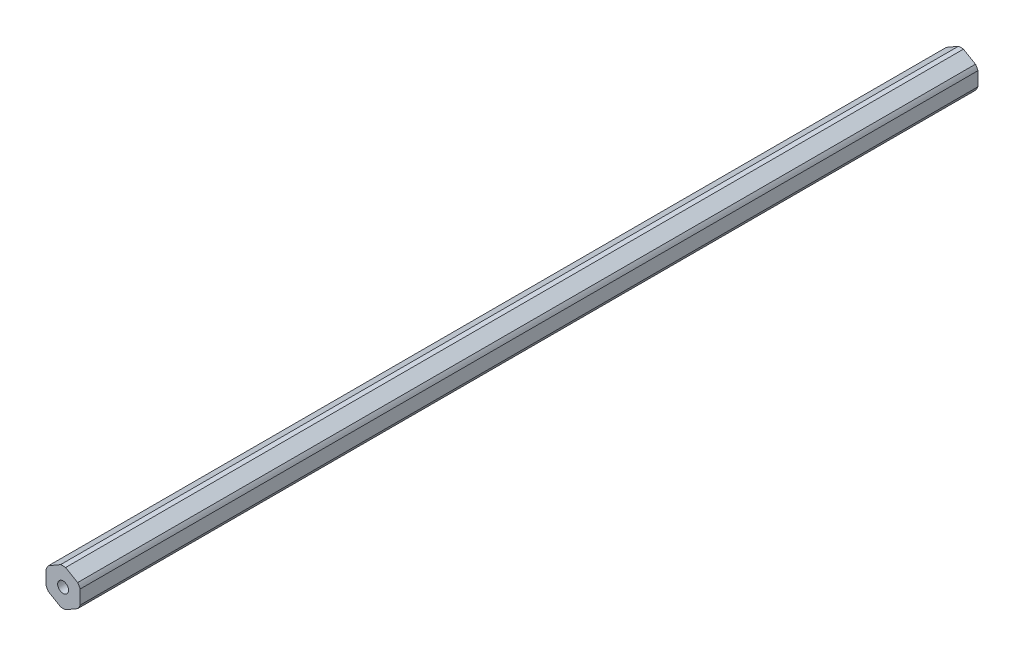
SolidWorks part; units mm, degrees
material "7075-T6 (SN)"
ref_plane "Front Plane" through (0, 0, 0) normal (0, 0, 1) x (1, 0, 0)
ref_plane "Top Plane" through (0, 0, 0) normal (0, 1, 0) x (1, 0, 0)
ref_plane "Right Plane" through (0, 0, 0) normal (1, 0, 0) x (0, 0, -1)
sketch "Sketch1" plane through (0, 0, 0) normal (0, 0, 1) x (1, 0, 0)
  line L1 (0, 7.3323) -> (-6.35, 3.6662)
  line L2 (-6.35, 3.6662) -> (-6.35, -3.6662)
  line L3 (-6.35, -3.6662) -> (0, -7.3323)
  line L4 (0, -7.3323) -> (6.35, -3.6662)
  line L5 (6.35, -3.6662) -> (6.35, 3.6662)
  line L6 (6.35, 3.6662) -> (0, 7.3323)
  circle A0 centre (0, 0) radius 6.35 construction
  circle A1 centre (0, 0) radius 6.858
  dimension "D1" = 12.7
  dimension "D2" = 13.716
extrude "Boss-Extrude1" add sketch "Sketch1" along normal mid plane 333.629 contours L5 A1 L6 L1 L2 L3 L4 region at (0, 0, 0)
sketch "Sketch2" plane through (0, 0, 166.8145) normal (0, 0, 1) x (1, 0, 0)
  circle A0 centre (0, 0) radius 2.0193
  dimension "D1" = 4.0386
extrude "Cut-Extrude1" cut sketch "Sketch2" against normal through all
